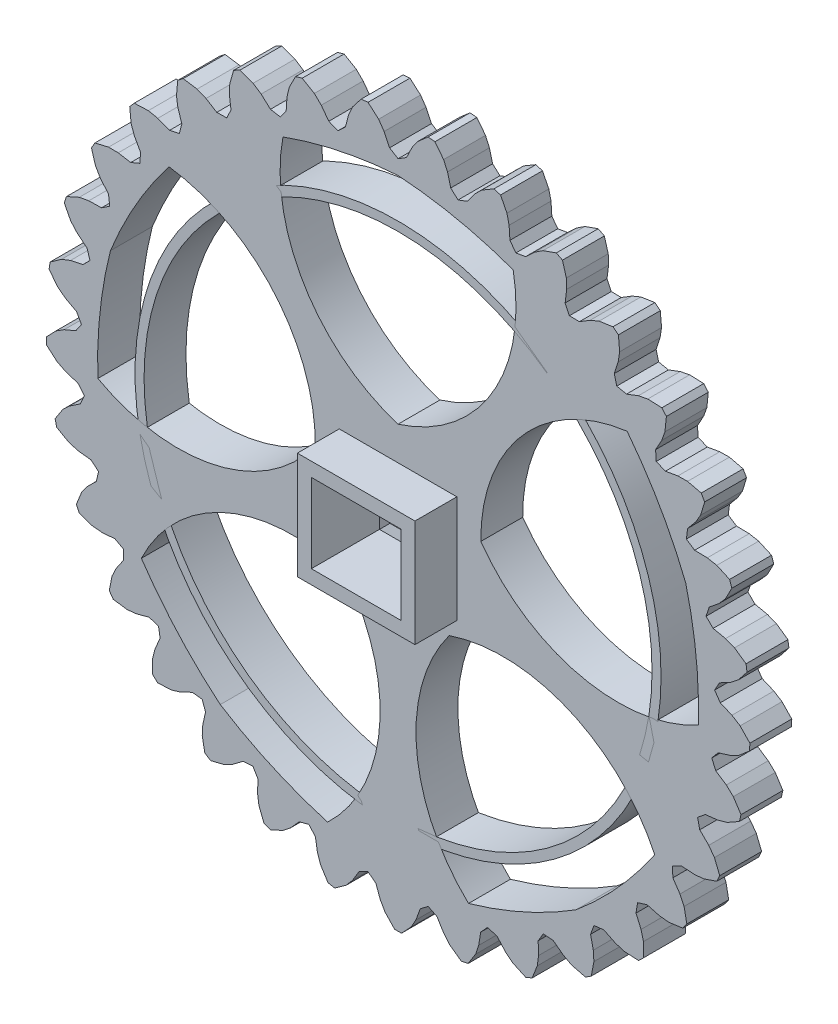
SolidWorks part; units mm, degrees
ref_plane "Front Plane" through (0, 0, 0) normal (0, 0, 1) x (1, 0, 0)
ref_plane "Top Plane" through (0, 0, 0) normal (0, 1, 0) x (1, 0, 0)
ref_plane "Right Plane" through (0, 0, 0) normal (1, 0, 0) x (0, 0, -1)
sketch "Sketch1" plane through (0, 0, 0) normal (0, 0, 1) x (1, 0, 0)
  line L1 (4.275, -3.775) -> (-4.275, -3.775)
  line L2 (4.275, -3.775) -> (4.275, 3.775)
  line L3 (4.275, 3.775) -> (-4.275, 3.775)
  line L4 (-4.275, -3.775) -> (-4.275, 3.775)
  circle A0 centre (0, 0) radius 33.6129
  point P3 (0, 3.775)
  point P9 (-4.275, 0)
  dimension "D1" = 67.2257
  dimension "D2" = 8.55
  dimension "D3" = 7.55
extrude "Boss-Extrude1" add sketch "Sketch1" along normal blind 4
sketch "Sketch2" plane through (0, 0, 0) normal (0, 0, 1) x (1, 0, 0)
  line L0 (0, 0) -> (0, 34.8589) construction
  line L1 (0, 30.2608) -> (-0.8069, 30.7591)
  line L2 (-0.8069, 30.7591) -> (-1.33, 31.849)
  line L3 (-1.33, 31.849) -> (-1.8557, 32.6046)
  line L4 (-1.8557, 32.6046) -> (-2.8665, 33.4904)
  line L5 (-2.8665, 33.4904) -> (-1.8557, 34.2629)
  line L6 (-1.8557, 34.2629) -> (0, 34.8589)
  line L7 (1.8557, 34.2629) -> (0, 34.8589)
  line L8 (2.8665, 33.4904) -> (1.8557, 34.2629)
  line L9 (1.8557, 32.6046) -> (2.8665, 33.4904)
  line L10 (1.33, 31.849) -> (1.8557, 32.6046)
  line L11 (0.8069, 30.7591) -> (1.33, 31.849)
  line L12 (0, 30.2608) -> (0.8069, 30.7591)
  circle A22 centre (0, 0) radius 33.6129 construction
  dimension "D5" = 0.5258
  dimension "D6" = 0.7556
  dimension "D9" = 0.5959
  dimension "D1" = 0.8069
  dimension "D2" = 0.4984
  dimension "D3" = 0.5231
  dimension "D4" = 1.0898
  dimension "D7" = 0.8858
  dimension "D8" = 1.8557
  dimension "D10" = 1.0107
  dimension "D11" = 0.7725
  dimension "D12" = 1.0107
extrude "Cut-Extrude1" cut sketch "Sketch2" along normal through all
pattern_circular "CirPattern1" count 33 over 360 about axis through (0, 0, 4) along (0, 0, -1) of "Cut-Extrude1"
sketch "Sketch3" plane through (0, 0, 0) normal (0, 0, 1) x (1, 0, 0)
  circle A0 centre (0, 0) radius 29.75
  dimension "D1" = 59.5
sketch "Sketch4" plane through (0, 0, 0) normal (0, 0, 1) x (1, 0, 0)
  line L0 (0, 0) -> (0, 28.8751) construction
  arc A1 (0, 28.8751) -> (-10.9903, 26.5681) centre (2.6519, -11.0897) ccw
  arc A2 (0, 28.8751) -> (10.9903, 26.5681) centre (-2.6519, -11.0897) cw
  arc A4 (0, 8.31) -> (-10.9903, 26.5681) centre (4.7786, 23.6232) cw
  arc A5 (0, 8.31) -> (10.9903, 26.5681) centre (-4.7786, 23.6232) ccw
  point P10 (0, 8.31)
extrude "Cut-Extrude2" cut sketch "Sketch4" along normal through all both
sketch "Sketch5" plane through (0, 0, 0) normal (0, 0, 1) x (1, 0, 0)
  circle A0 centre (0, 0) radius 25.1098
  circle A1 centre (0, 0) radius 24.2496
extrude "Boss-Extrude2" add sketch "Sketch5" along normal through all separate body
pattern_circular "CirPattern2" count 5 over 360 about axis through (0, 0, 4) along (0, 0, -1) of "Cut-Extrude2" reverse direction yes
chamfer "Chamfer1" distance 1.5 distance2 0.5 4 edges at (-4.275, 0, 0) (0, -3.775, 0) (4.275, 0, 0) (0, 3.775, 0) first distance on face at (-4.275, 0, 2) first distance on face at (0, -3.775, 2) first distance on face at (4.275, 0, 2) first distance on face at (0, 3.775, 2)
sketch "Sketch6" plane through (0, 0, 4) normal (0, 0, 1) x (1, 0, 0)
  line L1 (-4.275, 3.775) -> (4.275, 3.775)
  line L2 (-4.275, 3.775) -> (-4.275, -3.775)
  line L3 (-4.275, -3.775) -> (4.275, -3.775)
  line L4 (4.275, 3.775) -> (4.275, -3.775)
  line L5 (-5.6131, 5.1131) -> (5.6131, 5.1131)
  line L6 (-5.6131, 5.1131) -> (-5.6131, -5.1131)
  line L7 (-5.6131, -5.1131) -> (5.6131, -5.1131)
  line L8 (5.6131, 5.1131) -> (5.6131, -5.1131)
  dimension "D1" = 1.3381
  dimension "D2" = 1.3381
  dimension "D3" = 1.3381
  dimension "D4" = 1.3381
extrude "Boss-Extrude3" add sketch "Sketch6" along normal blind 4
equation "\"padding\"=1.33807"
equation "\"D1@Sketch6\"=\"padding\""
equation "\"D2@Sketch6\"=\"padding\""
equation "\"D3@Sketch6\"=\"padding\""
equation "\"D4@Sketch6\"=\"padding\""
